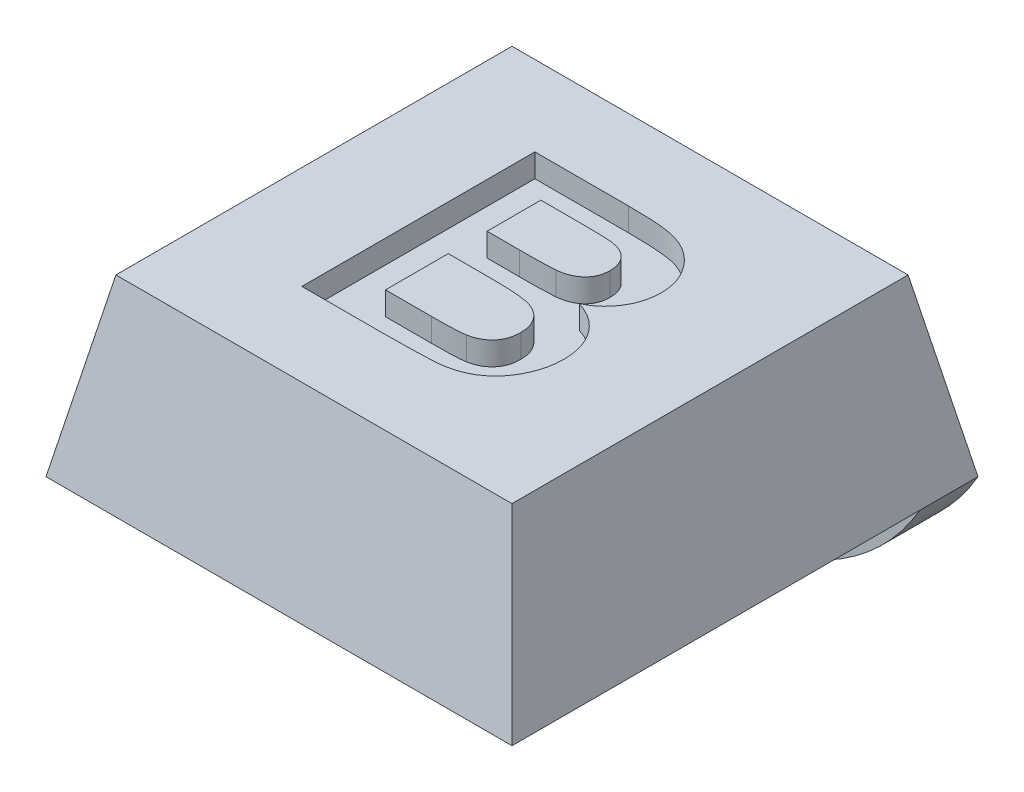
SolidWorks part; units mm, degrees
ref_plane "Front Plane" through (0, 0, 0) normal (0, 0, 1) x (1, 0, 0)
ref_plane "Top Plane" through (0, 0, 0) normal (0, 1, 0) x (1, 0, 0)
ref_plane "Right Plane" through (0, 0, 0) normal (1, 0, 0) x (0, 0, -1)
sketch "Sketch1" plane through (0, 0, 0) normal (0, 1, 0) x (1, 0, 0)
  line L1 (0, 0) -> (8, 0)
  line L2 (0, 0) -> (0, 8)
  line L3 (0, 8) -> (8, 8)
  line L4 (8, 0) -> (8, 8)
  dimension "D1" = 8
  dimension "D2" = 8
extrude "Boss-Extrude1" add sketch "Sketch1" along normal blind 3
sketch "Sketch2" plane through (0, 0, 0) normal (0, 0, 1) x (1, 0, 0)
  line L0 (0, 0) -> (0.6, 3)
  line L1 (0, 3) -> (8, 3) construction
  line L2 (0.6, 3) -> (0, 3)
  line L3 (0, 3) -> (0, 0)
  line L4 (8, 0) -> (7.4, 3)
  line L5 (7.4, 3) -> (8, 3)
  line L6 (8, 3) -> (8, 0)
  dimension "D1" = 0.6
  dimension "D2" = 0.6
extrude "Cut-Extrude1" cut sketch "Sketch2" against normal through all both and the other way through all
sketch "Sketch3" plane through (0, 0, 0) normal (1, 0, 0) x (0, 0, -1)
  line L0 (0, 0) -> (0.6, 3)
  line L1 (8, 3) -> (0, 3) construction
  line L2 (0.6, 3) -> (0, 3)
  line L3 (0, 3) -> (0, 0)
  line L4 (8, 3) -> (7.4, 3)
  line L5 (7.4, 3) -> (8, 0)
  line L6 (8, 3) -> (8, 0)
  dimension "D1" = 0.6
  dimension "D2" = 0.6
extrude "Cut-Extrude2" cut sketch "Sketch3" along normal blind 11
sketch "Sketch4" plane through (0, 0, 0) normal (0, -1, 0) x (1, 0, 0)
  line L0 (8, 0) -> (8, -8) construction
  line L3 (0, 0) -> (8, 0) construction
  circle A0 centre (4, -3.75) radius 1.75
  dimension "D1" = 3.5
  dimension "D2" = 4
  dimension "D3" = 3.75
extrude "Cut-Extrude3" cut sketch "Sketch4" against normal blind 0.4
sketch "Sketch5" plane through (0, 0, 0) normal (0, -1, 0) x (1, 0, 0)
  line L0 (8, 0) -> (8, -8) construction
  line L1 (0, -8) -> (8, -8)
  line L2 (0, -8) -> (0, -7)
  line L3 (0, -7) -> (8, -7)
  line L4 (8, -8) -> (8, -7)
  dimension "D1" = 1
extrude "Boss-Extrude2" add sketch "Sketch5" along normal blind 2
fillet "Fillet1" radius 4 2 edges at (8, -2, -7.5) (0, -2, -7.5)
sketch "Sketch6" plane through (0, 3, 0) normal (0, 1, 0) x (1, 0, 0)
  text T0 "B" font "Arial" height 4
extrude "Cut-Extrude4" cut sketch "Sketch6" against normal blind 0.4
